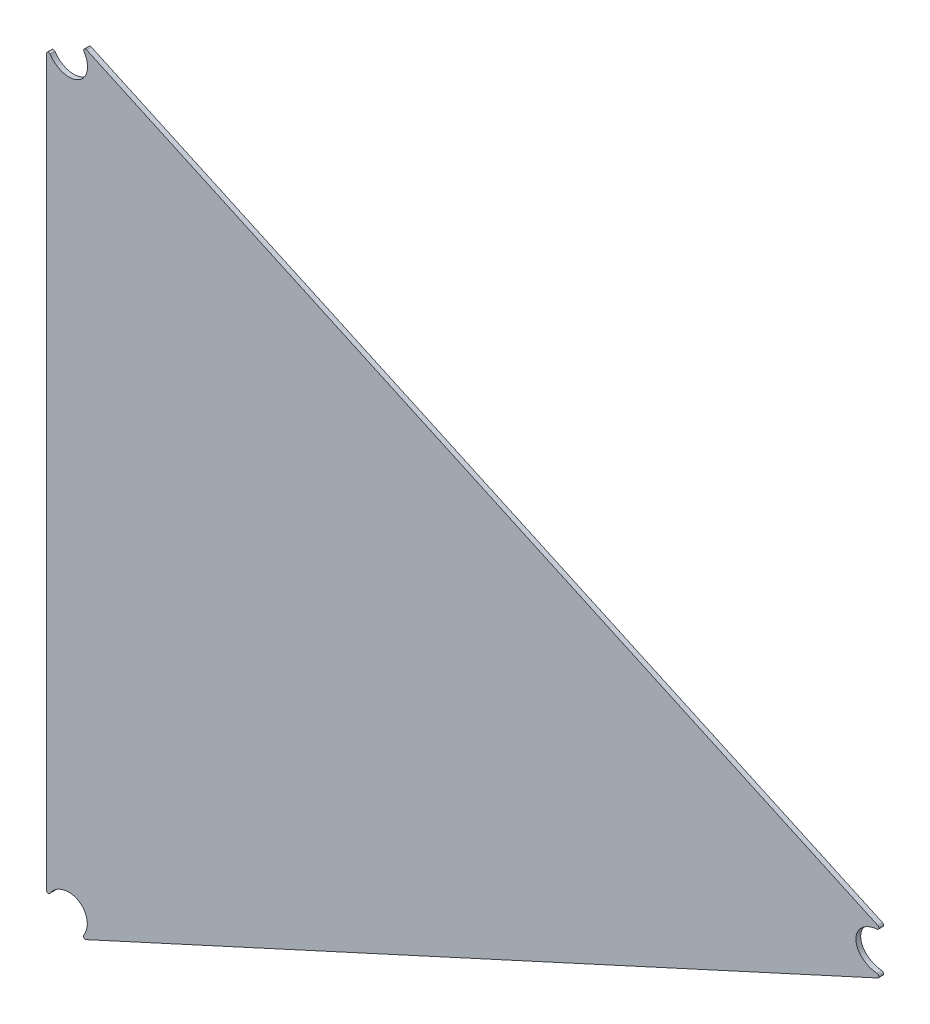
SolidWorks part; units mm, degrees
ref_plane "Front Plane" through (0, 0, 0) normal (0, 0, 1) x (1, 0, 0)
ref_plane "Top Plane" through (0, 0, 0) normal (0, 1, 0) x (1, 0, 0)
ref_plane "Right Plane" through (0, 0, 0) normal (1, 0, 0) x (0, 0, -1)
sketch "Sketch2" plane through (0, 0, 0) normal (0, 0, 1) x (1, 0, 0)
  line L0 (-248.5315, 247.553) -> (-248.6827, -247.4314)
  line L1 (-230.4044, -258.0646) -> (308.8333, -11.0849)
  line L2 (-230.2494, 258.1767) -> (308.8375, 11.083)
  spline S1 degree 3 poles (285.7631, 0) (285.7631, 25.4) (316.7708, 25.4) (316.7708, 0) (316.7708, -25.4) (285.7631, -25.4) (285.7631, 0) (285.7631, 25.4) (316.7708, 25.4) knots -0.5 0 0 0 0.5 0.5 0.5 1 1 1 1.5 1.5 1.5 weights 1 0.333333 0.333333 1 0.333333 0.333333 1 0.333333 0.333333 only from (285.7631, 0) to (285.7631, 0)
  spline S3 degree 3 poles (-224.1534, -237.5678) (-208.489, -257.5625) (-230.5174, -274.8202) (-246.1819, -254.8256) (-261.8463, -234.8309) (-239.8178, -217.5732) (-224.1534, -237.5678) (-208.489, -257.5625) (-230.5174, -274.8202) knots -0.5 0 0 0 0.5 0.5 0.5 1 1 1 1.5 1.5 1.5 weights 1 0.333333 0.333333 1 0.333333 0.333333 1 0.333333 0.333333 only from (-224.1534, -237.5678) to (-224.1534, -237.5678)
  spline S5 degree 3 poles (-224.0022, 237.6817) (-239.6667, 217.687) (-261.6951, 234.9448) (-246.0307, 254.9395) (-230.3663, 274.9341) (-208.3378, 257.6763) (-224.0022, 237.6817) (-239.6667, 217.687) (-261.6951, 234.9448) knots -0.5 0 0 0 0.5 0.5 0.5 1 1 1 1.5 1.5 1.5 weights 1 0.333333 0.333333 1 0.333333 0.333333 1 0.333333 0.333333 only from (-224.0022, 237.6817) to (-224.0022, 237.6817)
extrude "Boss-Extrude1" add sketch "Sketch2" along normal blind 3.175 contours L1 L2 L0 region at (-54.9928, 0.037, 0)
fillet "Fillet1" radius 1.27 6 edges at (-230.2494, 258.1767, 1.5875) (-248.5315, 247.553, 1.5875) (308.8333, -11.0849, 1.5875) (308.8375, 11.083, 1.5875) (-248.6827, -247.4314, 1.5875) (-230.4044, -258.0646, 1.5875)
